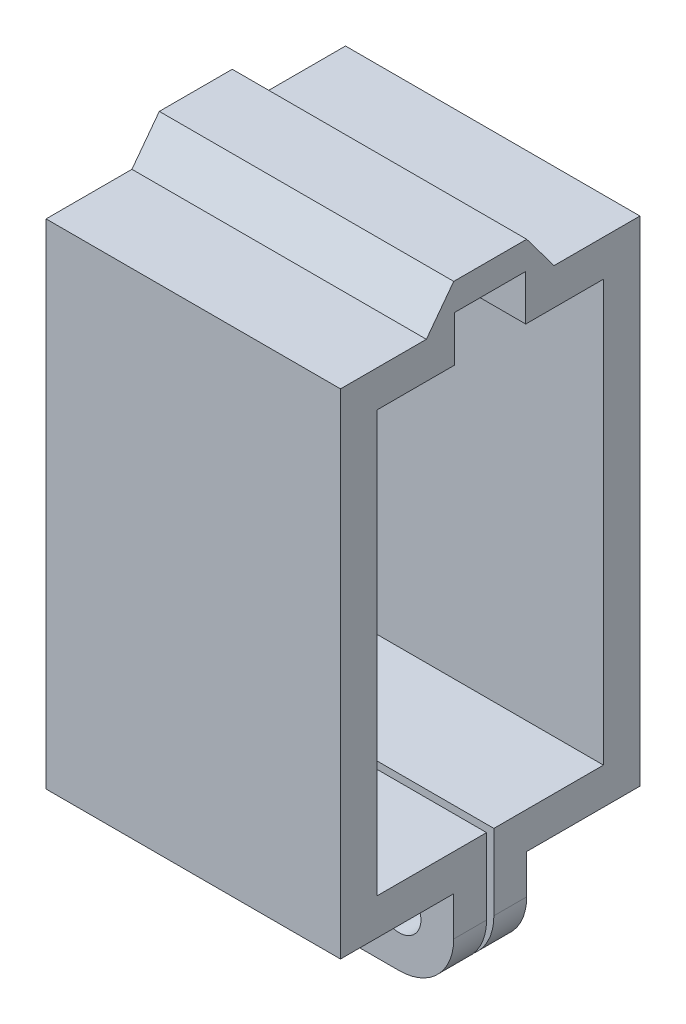
SolidWorks part; units mm, degrees
ref_plane "Front Plane" through (0, 0, 0) normal (0, 0, 1) x (1, 0, 0)
ref_plane "Top Plane" through (0, 0, 0) normal (0, 1, 0) x (1, 0, 0)
ref_plane "Right Plane" through (0, 0, 0) normal (1, 0, 0) x (0, 0, -1)
sketch "Sketch1" plane through (0, 0, 0) normal (1, 0, 0) x (0, 0, -1)
  line L0 (6.2079, 6.2079) -> (-6.2079, 6.2079)
  line L1 (-6.2079, 6.2079) -> (-6.2079, -16.8632)
  line L2 (-6.2079, -16.8632) -> (6.2079, -16.8632)
  line L3 (6.2079, -16.8632) -> (6.2079, 6.2079)
  line L4 (6.0579, 6.0579) -> (-6.0579, 6.0579)
  line L5 (-6.0579, 6.0579) -> (-6.0579, -16.7132)
  line L6 (-6.0579, -16.7132) -> (6.0579, -16.7132)
  line L7 (6.0579, -16.7132) -> (6.0579, 6.0579)
  line L8 (6.0579, 6.0579) -> (-6.0579, 6.0579) construction
  line L9 (-6.0579, 6.0579) -> (-6.0579, -16.7132) construction
  line L10 (-6.0579, -16.7132) -> (6.0579, -16.7132) construction
  line L11 (6.0579, -16.7132) -> (6.0579, 6.0579) construction
  line L12 (8.2079, 8.2079) -> (-8.2079, 8.2079)
  line L13 (-8.2079, 8.2079) -> (-8.2079, -18.8632)
  line L14 (-8.2079, -18.8632) -> (8.2079, -18.8632)
  line L15 (8.2079, -18.8632) -> (8.2079, 8.2079)
  dimension "D1" = 0
  dimension "D2" = 0.15
  dimension "D3" = 2
extrude "Boss-Extrude1" add sketch "Sketch1" along normal up to surface (16.1417 mm away)
sketch "Sketch2" plane through (16.1417, 0, 0) normal (1, 0, 0) x (0, 0, -1)
  line L0 (8.2079, 8.2079) -> (-8.2079, 8.2079) construction
  line L1 (-3.5, 8.2079) -> (3.5, 8.2079)
  line L3 (-2, 10.2079) -> (2, 10.2079)
  line L5 (-3.5, 8.2079) -> (-2, 10.2079)
  line L6 (3.5, 8.2079) -> (2, 10.2079)
  line L7 (0, 10.2079) -> (0, 8.2079) construction
  point P1 (-2, 10.3079)
  point P6 (0, 8.2079)
  dimension "D1" = 2
  dimension "D2" = 4
  dimension "D3" = 7
extrude "Boss-Extrude2" add sketch "Sketch2" against normal up to surface (16.1417 mm away) up to face at (0, -5.3276, 0)
sketch "Sketch3" plane through (16.1417, 0, 0) normal (1, 0, 0) x (0, 0, -1)
  line L0 (-1.4478, 8.2079) -> (1.4478, 8.2079) construction
  line L1 (-1.9478, 5.5579) -> (1.9478, 5.5579)
  line L2 (1.9478, 5.5579) -> (1.9478, 8.7079)
  line L3 (-1.9478, 8.7079) -> (1.9478, 8.7079)
  line L4 (-1.4478, 6.0579) -> (1.4478, 6.0579)
  line L5 (1.4478, 6.0579) -> (1.4478, 12.1539)
  line L6 (1.4478, 12.1539) -> (-1.4478, 12.1539)
  line L7 (-1.4478, 12.1539) -> (-1.4478, 6.0579)
  line L8 (-1.4478, 6.0579) -> (1.4478, 6.0579) construction
  line L9 (1.4478, 6.0579) -> (1.4478, 8.2079) construction
  line L11 (-1.4478, 8.2079) -> (-1.4478, 6.0579) construction
  line L12 (-1.9478, 8.7079) -> (-1.9478, 5.5579)
  line L13 (2, 10.2079) -> (-2, 10.2079) construction
  dimension "D2" = 0.5
  dimension "D3" = 1.5
  dimension "D1" = 0
extrude "Cut-Extrude1" cut sketch "Sketch3" against normal through all
sketch "Sketch4" plane through (16.1417, 0, 0) normal (1, 0, 0) x (0, 0, -1)
  line L0 (-8.2079, -18.8632) -> (8.2079, -18.8632) construction
  line L1 (-2, -18.8632) -> (2, -18.8632)
  line L2 (-2, -18.8632) -> (-2, -24.0132)
  line L3 (-2, -24.0132) -> (2, -24.0132)
  line L4 (2, -18.8632) -> (2, -24.0132)
  point P6 (0, -18.8632)
  dimension "D1" = 5.15
  dimension "D2" = 4
extrude "Boss-Extrude3" add sketch "Sketch4" against normal up to surface (16.1417 mm away) up to face at (0, 1.9401, 0)
sketch "Sketch5" plane through (16.1417, 0, 0) normal (1, 0, 0) x (0, 0, -1)
  line L0 (-6.2079, -16.8632) -> (6.2079, -16.8632) construction
  line L1 (-0.2, -16.8632) -> (0.2, -16.8632)
  line L2 (-0.2, -16.8632) -> (-0.2, -24.0132)
  line L3 (-0.2, -24.0132) -> (0.2, -24.0132)
  line L4 (0.2, -16.8632) -> (0.2, -24.0132)
  line L5 (-2, -24.0132) -> (2, -24.0132) construction
  point P8 (0, -16.8632)
  point P9 (0, 0)
  dimension "D1" = 0.4
fillet "Fillet1" radius 3 2 edges at (0, -24.0132, 0) (16.1417, -24.0132, 0)
extrude "Cut-Extrude3" cut sketch "Sketch5" against normal through all
hole_wizard "M2 Clearance Hole1" positions "Sketch6" profile "Sketch7" hole size "M2" standard "ANSI Metric" end condition through all
sketch "Sketch6" plane through (0, 0, -2) normal (0, 0, -1) x (-1, 0, 0)
  point P0 (-13.1417, -21.0132)
  point P3 (-3, -21.0132)
sketch "Sketch7" plane through (13.1417, -21.0132, -2) normal (1, 0, 0) x (0, 1, 0)
  line L0 (0, 0) -> (0, 10.2079)
  line L1 (0, 10.2079) -> (1.2, 10.2079)
  line L2 (1.2, 10.2079) -> (1.2, 0)
  line L5 (1.2, 0) -> (0, 0)
  line L11 (0, -6.35) -> (0, 107.95) construction
  dimension "Thru Hole Dia." = 2.4
  dimension "Thru Hole Depth" = 10.2079
